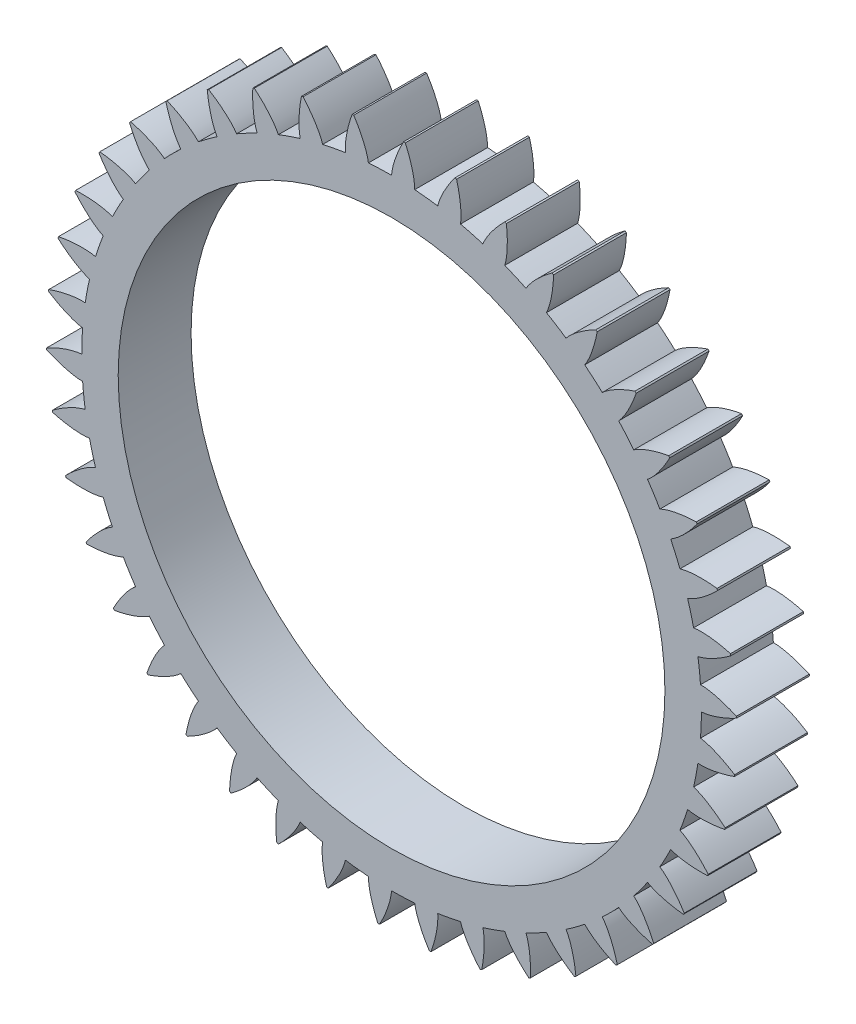
SolidWorks part; units mm, degrees
ref_plane "Front Plane" through (0, 0, 0) normal (0, 0, 1) x (1, 0, 0)
ref_plane "Top Plane" through (0, 0, 0) normal (0, 1, 0) x (1, 0, 0)
ref_plane "Right Plane" through (0, 0, 0) normal (1, 0, 0) x (0, 0, -1)
sketch "Sketch1" plane through (0, 0, 0) normal (0, 0, 1) x (1, 0, 0)
  line L0 (0, 0) -> (47.3193, -1.7706) construction
  line L1 (0, 0) -> (47.3193, 1.7706) construction
  line L2 (0, 0) -> (47.3193, -1.7706) construction
  line L3 (0, 0) -> (47.3524, 0) construction
  line L4 (0, 0) -> (47.0546, 5.3018) construction
  line L5 (0, 0) -> (47.3193, 1.7706)
  line L6 (42.4798, -1.5895) -> (37.4833, -1.4025)
  circle A0 centre (0, 0) radius 45.2 construction
  circle A1 centre (0, 0) radius 42.5095 construction
  circle A2 centre (0, 0) radius 42.4741 construction
  circle A3 centre (0, 0) radius 47.3524 construction
  arc A4 (42.5059, 0.5579) -> (42.4798, -1.5895) centre (0, 0) cw
  arc A5 (47.2632, 2.9041) -> (47.0335, -5.4865) centre (0, 0) cw
  arc A6 (37.4833, -1.4025) -> (37.4833, 1.4025) centre (0, 0) ccw
  spline S0 degree 4 poles (42.4741, 0) (42.5302, 0.0017) (42.6422, 0.0081) (42.9552, 0.0423) (43.546, 0.1494) (44.436, 0.3854) (45.6255, 0.8173) (47.1022, 1.5003) (48.755, 2.4501) (50.4757, 3.6438) (52.2195, 5.0775) (53.8537, 6.6343) (55.3803, 8.2963) (56.8717, 10.1359) (58.5748, 12.5231) (60.3856, 15.5166) (62.1816, 19.1625) (63.799, 23.3792) (65.0524, 27.7173) (65.9558, 32.1409) (66.5234, 36.6196) (66.7382, 40.5636) (66.7293, 43.9479) (66.5972, 46.7643) (66.4185, 49.0128) (66.1681, 51.2546) (65.8479, 53.487) (65.4591, 55.7094) (65.0607, 57.6414) (64.6778, 59.2907) (64.3799, 60.4692) (64.1876, 61.1947) (64.0217, 61.8024) (63.8414, 62.4443) (63.6884, 62.9728) (63.3886, 63.9768) (63.1489, 64.7323) (62.847, 65.6664) (62.5677, 66.4852) (62.2579, 67.3724) (61.953, 68.206) (61.7078, 68.8614) (61.5473, 69.276) (61.4636, 69.4921) knots 0 0 0 0 0 0.002802 0.005604 0.015718 0.02996 0.048734 0.068727 0.096889 0.125051 0.153212 0.181374 0.209535 0.237696 0.271429 0.327752 0.384075 0.440398 0.496721 0.553044 0.609367 0.66569 0.693852 0.722013 0.750174 0.778336 0.806497 0.834659 0.86282 0.876901 0.890982 0.895509 0.900036 0.909091 0.920455 0.931818 0.943182 0.954545 0.965909 0.977273 0.988636 1 1 1 1 1 construction
  spline S1 degree 4 poles (42.4741, 0) (42.5302, 0.0017) (42.6422, 0.0081) (42.9552, 0.0423) (43.546, 0.1494) (44.436, 0.3854) (45.6255, 0.8173) (47.1022, 1.5003) (48.755, 2.4501) (50.4757, 3.6438) (52.2195, 5.0775) (53.8537, 6.6343) (55.3803, 8.2963) (56.8717, 10.1359) (58.5748, 12.5231) (60.3856, 15.5166) (62.1816, 19.1625) (63.799, 23.3792) (65.0524, 27.7173) (65.9558, 32.1409) (66.5234, 36.6196) (66.7382, 40.5636) (66.7293, 43.9479) (66.5972, 46.7643) (66.4185, 49.0128) (66.1681, 51.2546) (65.8479, 53.487) (65.4591, 55.7094) (65.0607, 57.6414) (64.6778, 59.2907) (64.3799, 60.4692) (64.1876, 61.1947) (64.0217, 61.8024) (63.9109, 62.1968) (63.8419, 62.4392) (63.7962, 62.5976) knots 0 0 0 0 0 0.002802 0.005604 0.015718 0.02996 0.048734 0.068727 0.096889 0.125051 0.153212 0.181374 0.209535 0.237696 0.271429 0.327752 0.384075 0.440398 0.496721 0.553044 0.609367 0.66569 0.693852 0.722013 0.750174 0.778336 0.806497 0.834659 0.86282 0.876901 0.890982 0.895509 0.900036 0.909091 0.909091 0.909091 0.909091 0.909091
  dimension "pitchRadius" = 45.2
  dimension "addendumRadius" = 47.3524
  dimension "dedendumRadius" = 42.5095
  dimension "baseRadius" = 42.4741
  dimension "D1" = 4.286
  dimension "D2" = 2.143
  dimension "toothArc" = 8.571
  dimension "D3" = 5
extrude "Boss-Extrude1" add sketch "Sketch1" along normal blind 10 contours S1 A5 L5 A6 L6 A4 region at (41.1156, 0.2616, 0)
mirror "Mirror1" about plane through (0, 0, 10) normal (-0.0374, 0.9993, 0) of "Boss-Extrude1"
pattern_circular "CirPattern2" count 42 over 360 about axis through (0, 0, 10) along (0, 0, -1) of "Mirror1", "Boss-Extrude1"
ref_axis "Axis1" through (0, 0, 0) along (0, 0, 1)
equation "\"D1@Sketch1\"=\"toothArc@Sketch1\"/2"
equation "\"D2@Sketch1\"=\"toothArc@Sketch1\"/4"
equation "\"pitchRadius\"= 4.52"
equation "\"nTeeth\"= 42"
equation "\"pressureAngle\"= 20"
equation "\"baseRadius\"= \"pitchRadius\" * cos ( \"pressureAngle\" )"
equation "\"diametralPitch\"= \"nTeeth\" / ( 2 * \"pitchRadius\" )'note units: cm^-1"
equation "\"dedendum\"= 1.25 / \"diametralPitch\"'for full depth, 20 deg pressure angle"
equation "\"addendum\"= 1 / \"diametralPitch\""
equation "\"pitchRadius@Sketch1\"= \"pitchRadius\""
equation "\"addendumRadius@Sketch1\"= \"pitchRadius\" + \"addendum\""
equation "\"dedendumRadius@Sketch1\"= \"pitchRadius\" - \"dedendum\""
equation "\"baseRadius@Sketch1\"= \"baseRadius\""
equation "\"toothArc@Sketch1\"=360/\"nTeeth\""
